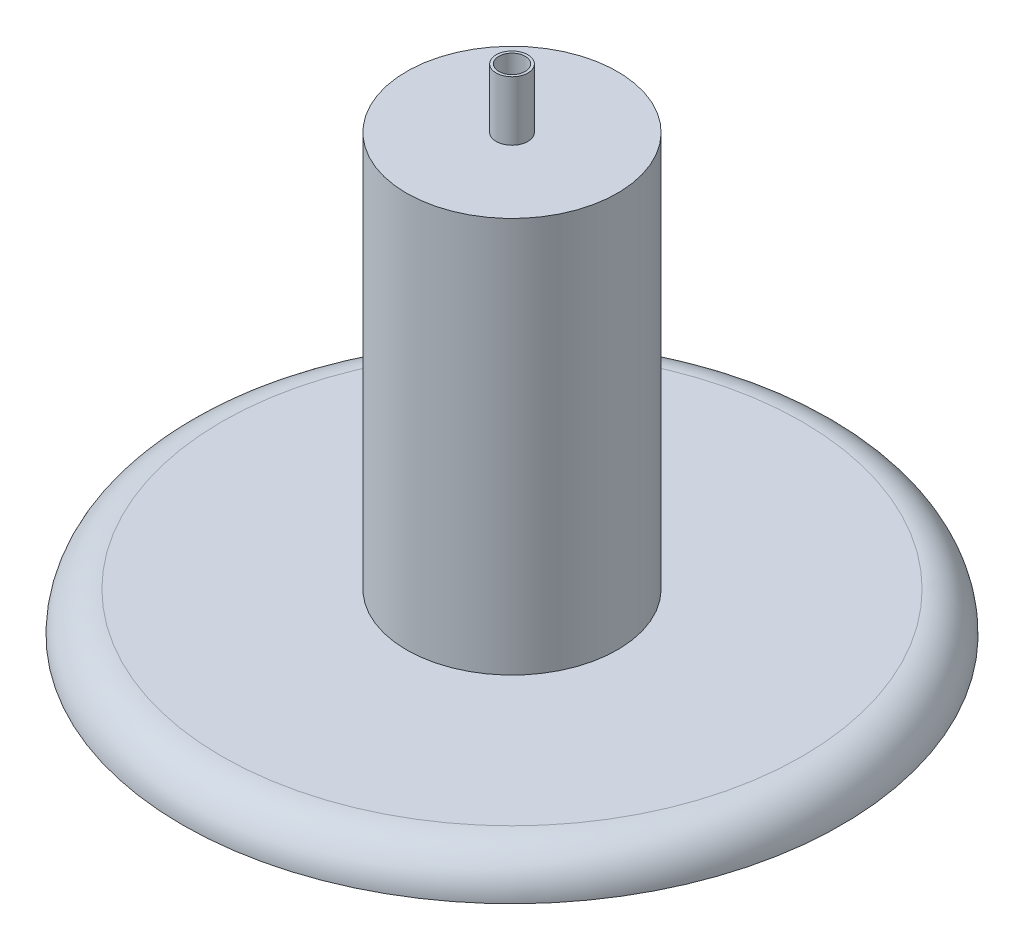
SolidWorks part; units mm, degrees
ref_plane "前视基准面" through (0, 0, 0) normal (0, 0, 1) x (1, 0, 0)
ref_plane "上视基准面" through (0, 0, 0) normal (0, 1, 0) x (1, 0, 0)
ref_plane "右视基准面" through (0, 0, 0) normal (1, 0, 0) x (0, 0, -1)
sketch "草图1" plane through (0, 0, 0) normal (0, 1, 0) x (1, 0, 0)
  circle A0 centre (0, 0) radius 250
  dimension "D1" = 500
extrude "凸台-拉伸2" add sketch "草图1" along normal blind 30
fillet "圆角1" radius 30 1 edges at (0, 30, 250)
sketch "草图4" plane through (0, 30, 0) normal (0, 1, 0) x (1, 0, 0)
  circle A0 centre (0, 0) radius 80
  dimension "D1" = 160
extrude "凸台-拉伸4" add sketch "草图4" along normal blind 300
sketch "草图5" plane through (0, 330, 0) normal (0, 1, 0) x (1, 0, 0)
  circle A0 centre (0, 0) radius 12
  dimension "D1" = 24
extrude "凸台-拉伸6" add sketch "草图5" along normal blind 45
sketch "草图6" plane through (0, 375, 0) normal (0, 1, 0) x (1, 0, 0)
  circle A1 centre (0, 0) radius 12 construction
  circle A2 centre (0, 0) radius 10
  circle A3 centre (0, 0) radius 10
  circle A4 centre (0, 0) radius 12
  dimension "D1" = 2
extrude "切除-拉伸2" cut sketch "草图6" against normal blind 45 contours A3 | A3 region at (0, 375, 0)
